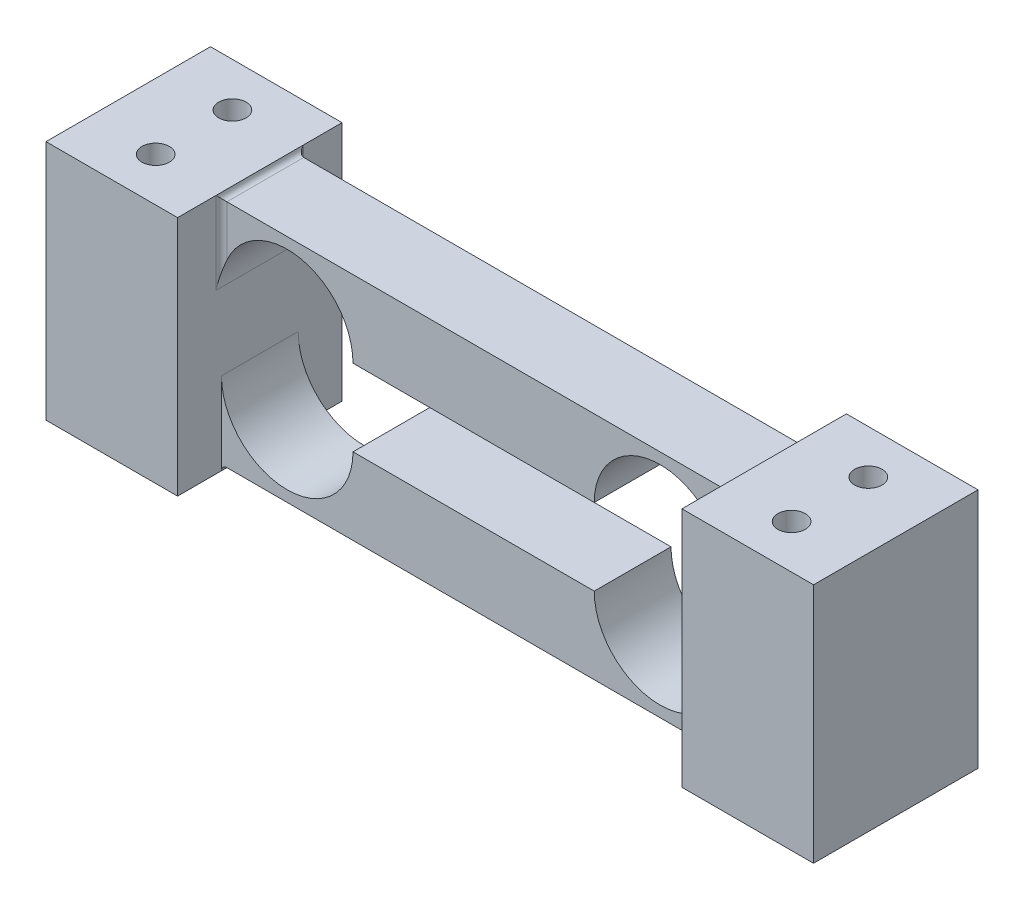
SolidWorks part; units mm, degrees
other "Markup1"
sketch "Sketch6" plane through (0, 6, 0) normal (-0.1374, 0.9905, 0.0006) x (-0.9877, -0.137, 0.0755)
material "6061-T6 (SS)"
ref_plane "Front Plane" through (0, 0, 0) normal (0, 0, 1) x (1, 0, 0)
ref_plane "Top Plane" through (0, 0, 0) normal (0, 1, 0) x (1, 0, 0)
ref_plane "Right Plane" through (0, 0, 0) normal (1, 0, 0) x (0, 0, -1)
sketch "Sketch1" plane through (0, 0, 0) normal (0, 1, 0) x (1, 0, 0)
  line L0 (0, 0) -> (0, 15)
  line L1 (0, 15) -> (12, 15)
  line L2 (12, 11) -> (58, 11)
  line L3 (58, 0) -> (70, 0)
  line L4 (70, 0) -> (70, 15)
  line L5 (0, 7.5) -> (70, 7.5) construction
  line L6 (58, 15) -> (70, 15)
  line L7 (12, 4) -> (58, 4)
  line L8 (0, 0) -> (12, 0)
  line L11 (12, 11) -> (12, 15)
  line L12 (12, 4) -> (12, 0)
  line L13 (58, 4) -> (58, 0)
  line L14 (58, 11) -> (58, 15)
  dimension "D3" = 7
  dimension "D1" = 12
  dimension "D2" = 70
  dimension "D4" = 15
extrude "Boss-Extrude1" add sketch "Sketch1" along normal blind 22
hole_wizard "M3 Tapped Hole1" positions "Sketch3" profile "Sketch4" tap size "M3" standard "AS" end condition through all
sketch "Sketch3" plane through (0, 22, 0) normal (0, 1, 0) x (1, 0, 0)
  line L0 (6, 4) -> (6, 11) construction
  line L2 (64, 11) -> (64, 4) construction
  line L6 (0, 15) -> (0, 0) construction
  line L7 (64, 11) -> (64, 15) construction
  line L8 (70, 15) -> (58, 15) construction
  line L10 (64, 4) -> (64, 0) construction
  line L11 (58, 0) -> (70, 0) construction
  line L13 (64, 4) -> (58, 4) construction
  line L15 (64, 4) -> (70, 4) construction
  line L16 (70, 0) -> (70, 15) construction
  line L18 (58, 4) -> (58, 0) construction
  line L21 (6, 4) -> (0, 4) construction
  line L23 (6, 4) -> (12, 4) construction
  line L24 (12, 0) -> (12, 4) construction
  point P0 (6, 11)
  point P2 (6, 4)
  point P4 (64, 11)
  point P6 (64, 4)
  point P23 (6, 7.5)
  point P26 (0, 7.5)
  point P77 (6, 3.0745)
  dimension "D2" = 7
  dimension "D1" = 7
sketch "Sketch4" plane through (6, 22, -11) normal (1, 0, 0) x (0, 0, 1)
  line L0 (0, 0) -> (0, 22)
  line L1 (0, 22) -> (1.25, 22)
  line L2 (1.25, 22) -> (1.25, 0)
  line L5 (1.25, 0) -> (0, 0)
  line L11 (0, -6.35) -> (0, 107.95) construction
  dimension "Thru Tap Drill Dia." = 2.5
  dimension "Thru Tap Drill Depth" = 22
cosmetic thread "Hole Thread1" parameters "D2"=3
cosmetic thread "Hole Thread2" parameters "D2"=3
cosmetic thread "Hole Thread3" parameters "D2"=3
cosmetic thread "Hole Thread4" parameters "D2"=3
sketch "Sketch10" plane through (0, 0, -11) normal (0, 0, -1) x (-1, 0, 0)
  line L0 (-12, 22) -> (-12, 0) construction
  line L1 (-58, 22) -> (-12, 22)
  line L2 (-58, 22) -> (-58, 21.5)
  line L3 (-58, 21.5) -> (-12, 21.5)
  line L4 (-12, 22) -> (-12, 21.5)
  line L5 (-58, 11) -> (-12, 11) construction
  line L6 (-58, 22) -> (-58, 0) construction
  line L7 (-58, 0.5) -> (-12, 0.5)
  line L8 (-12, 0) -> (-12, 0.5)
  line L9 (-58, 0) -> (-12, 0)
  line L10 (-58, 0) -> (-58, 0.5)
  dimension "D1" = 0.5
extrude "Cut-Extrude2" cut sketch "Sketch10" against normal up to next
sketch "Sketch11" plane through (0, 0, -11) normal (0, 0, -1) x (-1, 0, 0)
  line L0 (-12, 21.5) -> (-12, 0.5) construction
  line L1 (-58, 21.5) -> (-58, 0.5) construction
  line L2 (-12, 7.5) -> (-12, 14.5)
  line L3 (-24, 7.5) -> (-46, 7.5)
  line L4 (-58, 7.5) -> (-58, 14.5)
  line L5 (-46, 14.5) -> (-24, 14.5)
  line L6 (0, 22) -> (0, 0) construction
  line L7 (-12, 11) -> (0, 11) construction
  line L8 (-58, 21.5) -> (-12, 21.5) construction
  arc A0 (-12, 7.5) -> (-24, 7.5) centre (-18, 7.5) cw
  arc A1 (-12, 14.5) -> (-24, 14.5) centre (-18, 14.5) ccw
  arc A2 (-58, 7.5) -> (-46, 7.5) centre (-52, 7.5) ccw
  arc A3 (-58, 14.5) -> (-46, 14.5) centre (-52, 14.5) cw
  point P16 (-18, 20.5)
  dimension "D1" = 1
  dimension "D2" = 7
extrude "Cut-Extrude3" cut sketch "Sketch11" against normal up to next
fillet "Fillet2" radius 0.5 4 edges at (58, 21.5, -7.5) (12, 21.5, -7.5) (58, 0.5, -7.5) (12, 0.5, -7.5)
equation "\"D1@Sketch3\"=\"D2@Sketch3\""
